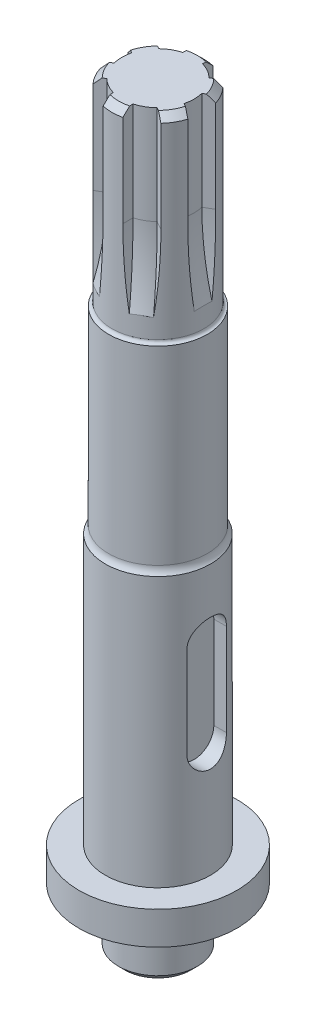
SolidWorks part; units mm, degrees
material "Alloy Steel"
ref_plane "Ön Düzlem" through (0, 0, 0) normal (0, 0, 1) x (1, 0, 0)
ref_plane "Üst Düzlem" through (0, 0, 0) normal (0, 1, 0) x (1, 0, 0)
ref_plane "Sağ Düzlem" through (0, 0, 0) normal (1, 0, 0) x (0, 0, -1)
sketch "Sketch1" plane through (0, 0, 0) normal (0, 1, 0) x (1, 0, 0)
  circle A0 centre (0, 0) radius 6
  dimension "D1" = 12
extrude "Boss-Extrude1" add sketch "Sketch1" along normal blind 9
sketch "Sketch2" plane through (0, 9, 0) normal (0, 1, 0) x (1, 0, 0)
  circle A0 centre (0, 0) radius 12
  dimension "D1" = 24
extrude "Boss-Extrude2" add sketch "Sketch2" along normal blind 5
sketch "Sketch3" plane through (0, 14, 0) normal (0, 1, 0) x (1, 0, 0)
  circle A0 centre (0, 0) radius 8
  dimension "D1" = 16
extrude "Boss-Extrude3" add sketch "Sketch3" along normal blind 41
sketch "Sketch4" plane through (0, 55, 0) normal (0, 1, 0) x (1, 0, 0)
  circle A0 centre (0, 0) radius 7.5
  dimension "D1" = 15
extrude "Boss-Extrude4" add sketch "Sketch4" along normal blind 30
sketch "Sketch5" plane through (0, 85, 0) normal (0, 1, 0) x (1, 0, 0)
  circle A0 centre (0, 0) radius 7
  dimension "D1" = 14
extrude "Boss-Extrude5" add sketch "Sketch5" along normal blind 30
chamfer "Chamfer1" distance 1 angle 45 1 edges at (0, 0, 6)
fillet "Fillet1" radius 1.5 1 edges at (0, 55, 7.5)
fillet "Fillet2" radius 0.5 1 edges at (0, 85, 7)
ref_plane "Plane1" through (8, 0, 0) normal (1, 0, 0) x (0, 0, -1)
sketch "Sketch7" plane through (8, 0, 0) normal (1, 0, 0) x (0, 0, -1)
  line L0 (0, 45) -> (0, 31) construction
  line L1 (3, 45) -> (3, 31)
  line L2 (-3, 45) -> (-3, 31)
  line L3 (-8, 55) -> (8, 55) construction
  arc A0 (3, 45) -> (-3, 45) centre (0, 45) ccw
  arc A1 (-3, 31) -> (3, 31) centre (0, 31) ccw
  point P3 (0, 38)
  dimension "D1" = 6
  dimension "D2" = 14
  dimension "D3" = 10
extrude "Cut-Extrude1" cut sketch "Sketch7" against normal blind 2.5
sketch "Sketch8" plane through (0, 115, 0) normal (0, 1, 0) x (1, 0, 0)
  line L0 (0, 7) -> (0, 5.5)
  line L1 (-1.5, 6.8374) -> (-1.5, 5.2915)
  line L2 (1.5, 6.8374) -> (1.5, 5.2915)
  line L3 (5.1714, 4.7177) -> (3.8326, 3.9448)
  line L4 (-1.5, 7.8607) -> (-1.5, 3.5743) construction
  line L5 (0, 7.8607) -> (0, 3.5743) construction
  line L6 (1.5, 7.8607) -> (1.5, 3.5743) construction
  line L7 (6.0622, 3.5) -> (4.7631, 2.75)
  line L8 (6.6714, 2.1197) -> (5.3326, 1.3467)
  line L9 (6.6714, -2.1197) -> (5.3326, -1.3467)
  line L10 (6.0622, -3.5) -> (4.7631, -2.75)
  line L11 (5.1714, -4.7177) -> (3.8326, -3.9448)
  line L12 (1.5, -6.8374) -> (1.5, -5.2915)
  line L13 (0, -7) -> (0, -5.5)
  line L14 (-1.5, -6.8374) -> (-1.5, -5.2915)
  line L15 (-5.1714, -4.7177) -> (-3.8326, -3.9448)
  line L16 (-6.0622, -3.5) -> (-4.7631, -2.75)
  line L17 (-6.6714, -2.1197) -> (-5.3326, -1.3467)
  line L18 (-6.6714, 2.1197) -> (-5.3326, 1.3467)
  line L19 (-6.0622, 3.5) -> (-4.7631, 2.75)
  line L20 (-5.1714, 4.7177) -> (-3.8326, 3.9448)
  circle A0 centre (0, 0) radius 7
  circle A1 centre (0, 0) radius 5.5
  point P49 (0, 0)
  circle M4 centre (0, 0) radius 7
  dimension "D1" = 11
  dimension "D2" = 14
  dimension "D5" = 6
  dimension "D3" = 1.5
  dimension "D4" = 1.5
extrude "Cut-Extrude2" cut sketch "Sketch8" against normal blind 15 contours A1 L9 L8 M4 | A1 L3 L2 M4 | A1 L1 L20 M4 | A1 L18 L17 M4 | A1 L15 L14 M4 | A1 L12 L11 M4 region at (3.111, 115, -5.3884) region at (-3.111, 115, -5.3884) region at (6.222, 115, 0) region at (-6.222, 115, 0) region at (-3.111, 115, 5.3884) region at (3.111, 115, 5.3884)
sketch "Sketch9" plane through (0, 100, 0) normal (0, 1, 0) x (1, 0, 0)
  line L0 (6.6714, 2.1197) -> (5.3326, 1.3467)
  line L2 (5.3326, -1.3467) -> (6.6714, -2.1197)
  line L4 (50, 2.1197) -> (50, 1.3467)
  line L5 (5.1714, -4.7177) -> (3.8326, -3.9448)
  line L6 (1.5, -5.2915) -> (1.5, -6.8374)
  line L7 (-1.5, -6.8374) -> (-1.5, -5.2915)
  line L8 (-3.8326, -3.9448) -> (-5.1714, -4.7177)
  line L9 (-6.6714, -2.1197) -> (-5.3326, -1.3467)
  line L10 (-5.3326, 1.3467) -> (-6.6714, 2.1197)
  line L11 (-5.1714, 4.7177) -> (-3.8326, 3.9448)
  line L12 (-1.5, 5.2915) -> (-1.5, 6.8374)
  line L13 (1.5, 6.8374) -> (1.5, 5.2915)
  line L14 (3.8326, 3.9448) -> (5.1714, 4.7177)
  line L15 (23.8337, -43.9746) -> (26.1663, -42.6279)
  line L16 (1.5, -6.8374) -> (5.1714, -4.7177)
  line L17 (-5.1714, -4.7177) -> (-1.5, -6.8374)
  line L18 (-26.1663, -42.6279) -> (-23.8337, -43.9746)
  line L19 (-50.0148, 0.5734) -> (-49.9732, -2.1197)
  line L20 (-26.1663, 42.6279) -> (-23.8337, 43.9746)
  line L21 (-5.1714, 4.7177) -> (-1.5, 6.8374)
  line L22 (23.8337, 43.9746) -> (26.1663, 42.6279)
  line L23 (1.5, 6.8374) -> (5.1714, 4.7177)
  arc A0 (6.6714, -2.1197) -> (6.6714, 2.1197) centre (0, 0) ccw
  arc A1 (5.3326, 1.3467) -> (5.3326, -1.3467) centre (0, 0) cw
  arc A2 (1.5, -6.8374) -> (5.1714, -4.7177) centre (0, 0) ccw
  arc A3 (-5.1714, -4.7177) -> (-1.5, -6.8374) centre (0, 0) ccw
  arc A4 (-6.6714, 2.1197) -> (-6.6714, -2.1197) centre (0, 0) ccw
  arc A5 (-1.5, 6.8374) -> (-5.1714, 4.7177) centre (0, 0) ccw
  arc A6 (5.1714, 4.7177) -> (1.5, 6.8374) centre (0, 0) ccw
  arc A7 (1.5, -5.2915) -> (3.8326, -3.9448) centre (0, 0) ccw
  arc A8 (-3.8326, -3.9448) -> (-1.5, -5.2915) centre (0, 0) ccw
  arc A9 (-5.3326, 1.3467) -> (-5.3326, -1.3467) centre (0, 0) ccw
  arc A10 (-1.5, 5.2915) -> (-3.8326, 3.9448) centre (0, 0) ccw
  arc A11 (1.5, 5.2915) -> (3.8326, 3.9448) centre (0, 0) cw
  circle A12 centre (0, 0) radius 50.0181
  point P35 (0, 0)
  dimension "D1" = 7
  dimension "D2" = 5.5
  dimension "D5" = 5.5
  dimension "D6" = 50
  dimension "D7" = 5.5
  dimension "D8" = 5.5
  dimension "D9" = 5.5
  dimension "D10" = 5.5
  dimension "D11" = 50
  dimension "D12" = 100.0363
  dimension "D14" = 50
  dimension "D15" = 50
  dimension "D3" = 50
  dimension "D13" = 50
  dimension "D4" = 6
revolve "Cut-Revolve3" cut sketch "Sketch9" angle 360 about L4
revolve "Cut-Revolve5" cut sketch "Sketch9<13>" angle 360 about L15 region at (3.0485, 100, 5.2802) region at (3.4015, 100, 5.8916)
sketch "Sketch9<13>" plane through (0, 100, 0) normal (0, 1, 0) x (1, 0, 0) same geometry as "Sketch9"
revolve "Cut-Revolve6" cut sketch "Sketch9<14>" angle 360 about L18 region at (-3.0485, 100, 5.2802) region at (-3.4015, 100, 5.8916)
sketch "Sketch9<14>" plane through (0, 100, 0) normal (0, 1, 0) x (1, 0, 0) same geometry as "Sketch9"
revolve "Cut-Revolve7" cut sketch "Sketch9<15>" angle 360 about L19 region at (-6.222, 100, 0)
sketch "Sketch9<15>" plane through (0, 100, 0) normal (0, 1, 0) x (1, 0, 0) same geometry as "Sketch9"
revolve "Cut-Revolve8" cut sketch "Sketch9<16>" angle 360 about L20 region at (-3.0485, 100, -5.2802) region at (-3.4015, 100, -5.8916)
sketch "Sketch9<16>" plane through (0, 100, 0) normal (0, 1, 0) x (1, 0, 0) same geometry as "Sketch9"
revolve "Cut-Revolve9" cut sketch "Sketch9<17>" angle 360 about L22 region at (3.0485, 100, -5.2802) region at (3.4015, 100, -5.8916)
sketch "Sketch9<17>" plane through (0, 100, 0) normal (0, 1, 0) x (1, 0, 0) same geometry as "Sketch9"
chamfer "Chamfer2" distance 1 angle 45 1 edges at (0, 115, 7)
chamfer "Chamfer3" distance 1 angle 45 1 edges at (6.0622, 115, 3.5)
chamfer "Chamfer4" distance 1 angle 45 1 edges at (6.0622, 115, -3.5)
chamfer "Chamfer5" distance 1 angle 45 1 edges at (0, 115, -7)
chamfer "Chamfer6" distance 1 angle 45 1 edges at (-6.0622, 115, -3.5)
chamfer "Chamfer7" distance 1 angle 45 1 edges at (-6.0622, 115, 3.5)
